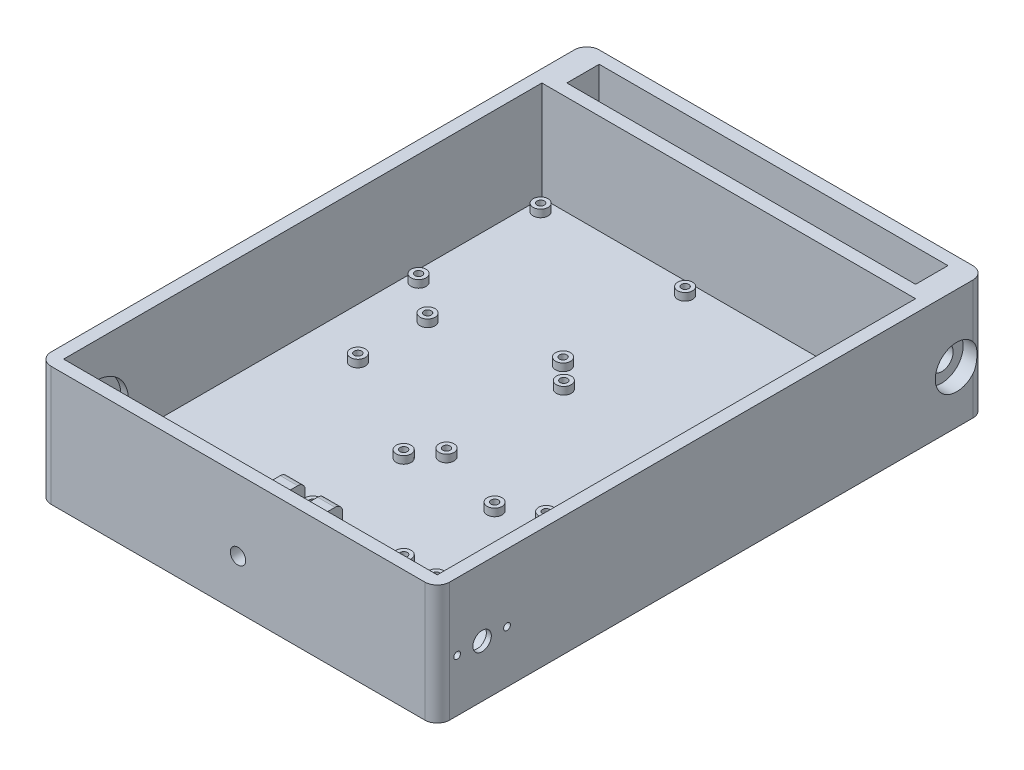
SolidWorks part; units mm, degrees
ref_plane "Front Plane" through (0, 0, 0) normal (0, 0, 1) x (1, 0, 0)
ref_plane "Top Plane" through (0, 0, 0) normal (0, 1, 0) x (1, 0, 0)
ref_plane "Right Plane" through (0, 0, 0) normal (1, 0, 0) x (0, 0, -1)
sketch "Main Body" plane through (0, 0, 0) normal (0, 1, 0) x (1, 0, 0)
  line L0 (-75, 110) -> (75, 110)
  line L1 (-75, -105) -> (75, -105)
  line L2 (-75, -105) -> (-75, 105)
  line L3 (-75, 105) -> (75, 105)
  line L4 (75, -105) -> (75, 105)
  line L5 (-75, -105) -> (75, 105) construction
  line L6 (-75, 105) -> (75, -105) construction
  line L7 (80, -105) -> (80, 105)
  line L8 (-75, -110) -> (75, -110)
  line L9 (-80, -105) -> (-80, 105)
  line L10 (-80, -110) -> (80, -110) construction
  line L11 (-80, -110) -> (-80, 110) construction
  line L12 (80, -110) -> (80, 110) construction
  line L13 (-80, 110) -> (80, 110) construction
  arc A0 (-75, -110) -> (-80, -105) centre (-75, -105) cw
  arc A1 (80, -105) -> (75, -110) centre (75, -105) cw
  arc A2 (75, 110) -> (80, 105) centre (75, 105) cw
  arc A3 (-75, 110) -> (-80, 105) centre (-75, 105) ccw
  point P0 (0, 0)
  dimension "D4" = 5
  dimension "D1" = 75
  dimension "D2" = 210
  dimension "D3" = 5
extrude "Boss-Extrude1" add sketch "Main Body" along normal blind 8 contours L1 L4 L3 L2 | L9 L8 L7 L0 L4 L1 L2 L3 region at (0, 0, -107.2797) region at (0, 0, 0)
extrude "Boss-Extrude3" add sketch "Main Body<4>" along normal blind 40 from surface starting at face at (0, 8, 0)
sketch "Main Body<4>" plane through (0, 0, 0) normal (0, 1, 0) x (1, 0, 0) same geometry as "Main Body"
sketch "Sketch1" plane through (75, 0, 0) normal (-1, 0, 0) x (0, 0, 1)
  line L0 (105, 48) -> (105, 8) construction
  line L1 (-105, 8) -> (105, 8) construction
  line L2 (79, 15.5) -> (105, 15.5)
  line L3 (79, 8) -> (105, 8)
  line L4 (79, 8) -> (79, 34)
  line L5 (79, 34) -> (105, 34)
  line L6 (105, 8) -> (105, 34)
  line L7 (79, 8) -> (105, 34) construction
  line L8 (79, 34) -> (105, 8) construction
  circle A0 centre (92, 21) radius 13
  line M2 (-105, 8) -> (105, 8)
  line M3 (105, 8) -> (105, 48)
  dimension "D1" = 26
  dimension "D2" = 7.5
extrude "Boss-Extrude4" add sketch "Sketch1" along normal up to surface (150 mm away) contours A0 L4 M2 | A0 L3 M3 region at (75, 10.5201, 82.0674) region at (75, 10.5201, 101.9326) up to face at (-75, 28, 0)
sketch "Sketch2" plane through (0, 0, 0) normal (1, 0, 0) x (0, 0, -1)
  line L0 (-105, 48) -> (-105, 15.5) construction
  line L1 (-105, 8) -> (-79, 8)
  line L2 (-105, 8) -> (-105, 15.5)
  line L3 (-105, 15.5) -> (-79, 15.5)
  line L4 (-79, 8) -> (-79, 15.5)
  line L5 (105, 8) -> (-79, 8) construction
  line L6 (-79, 8) -> (-79, 15.5) construction
  line L7 (-79, 15.5) -> (-80.2208, 15.5) construction
extrude "Cut-Extrude1" cut sketch "Sketch2" against normal mid plane 12
sketch "Sketch3" plane through (0, 8, 0) normal (0, 1, 0) x (1, 0, 0)
  line L0 (75, -105) -> (-75, -105) construction
  line L1 (-4, -79) -> (-11, -79)
  line L2 (-4, -79) -> (-4, -105)
  line L3 (-4, -105) -> (-11, -105)
  line L4 (-11, -79) -> (-11, -105)
  line L5 (0, 0) -> (0, -105) construction
  line L6 (-75, -79) -> (-6, -79) construction
  line L7 (11, -79) -> (11, -105)
  line L8 (4, -105) -> (11, -105)
  line L9 (4, -79) -> (4, -105)
  line L10 (4, -79) -> (11, -79)
  line L11 (-6, -103.7792) -> (-6, -92) construction
  dimension "D1" = 5
  dimension "D2" = 4
extrude "Boss-Extrude5" add sketch "Sketch3" along normal blind 20
sketch "Sketch4" plane through (0, 8, 0) normal (0, 1, 0) x (1, 0, 0)
  line L0 (-75, -105) -> (-75, 105) construction
  line L1 (-75, 92) -> (75, 92)
  line L2 (-75, 92) -> (-75, 87)
  line L3 (-75, 87) -> (75, 87)
  line L4 (75, 92) -> (75, 87)
  line L5 (75, 105) -> (75, -105) construction
  line L6 (-75, 105) -> (75, 105) construction
  dimension "D1" = 18
  dimension "D2" = 5
extrude "Boss-Extrude6" add sketch "Sketch4" along normal up to surface (40 mm away) up to face at (0, 48, 0)
sketch "Sketch5" plane through (80, 0, 0) normal (1, 0, 0) x (0, 0, -1)
  circle A0 centre (-92, 21) radius 3.5 construction
  circle A1 centre (-92, 21) radius 3.5
  circle A2 centre (-92, 21) radius 3.7
  dimension "D1" = 0.2
extrude "Cut-Extrude4" cut sketch "Sketch5" against normal up to next contours A1 | A2 A1 region at (80, 21, 92) region at (80, 21, 95.5953)
sketch "Sketch6" plane through (-75, 0, 0) normal (1, 0, 0) x (0, 0, -1)
  circle A0 centre (-92, 21) radius 13
  dimension "D1" = 26
extrude "Cut-Extrude5" cut sketch "Sketch6" against normal offset from surface (3 mm away) 2 up to face at (-80, 24, 0)
mirror "Mirror1" about plane through (0, 0, 0) normal (1, 0, 0) of "Cut-Extrude4"
sketch "Sketch8" plane through (75, 0, 0) normal (-1, 0, 0) x (0, 0, 1)
  circle A0 centre (92, 21) radius 13
  dimension "D1" = 26
extrude "Cut-Extrude6" cut sketch "Sketch8" against normal offset from surface (3 mm away) 2 up to face at (80, 21, 88.3)
sketch "Sketch10" plane through (80, 0, 0) normal (1, 0, 0) x (0, 0, -1)
  circle A1 centre (-82, 21) radius 1.25
  circle A2 centre (-82, 21) radius 1.25
  circle A3 centre (-102, 21) radius 1.25
  circle A4 centre (-102, 21) radius 1.25
  circle A5 centre (-92, 21) radius 12.5
  circle A6 centre (-92, 21) radius 12.5
  circle A63 centre (-102, 21) radius 1.35
  circle A64 centre (-82, 21) radius 1.35
  dimension "D1" = 0
  dimension "D2" = 0
  dimension "D3" = 0
  dimension "D4" = 0.1
  dimension "D5" = 0.1
extrude "Cut-Extrude7" cut sketch "Sketch10" against normal up to next contours A2 | A64 A2 | A4 | A63 A4 region at (80, 21, 82) region at (80, 21, 102) region at (80, 21, 103.3118) region at (80, 21, 83.3118)
mirror "Mirror3" about plane through (0, 0, 0) normal (1, 0, 0) of "Cut-Extrude7"
sketch "Sketch11" plane through (80, 0, 0) normal (1, 0, 0) x (0, 0, -1)
  circle A0 centre (98.5, 21) radius 4.5 construction
  circle A1 centre (98.5, 21) radius 4.5
  circle A3 centre (98.5, 21) radius 4.6
  dimension "D1" = 0.1
extrude "Cut-Extrude10" cut sketch "Sketch11" against normal through all contours A1 | A3 A1 region at (80, 21, -98.5) region at (80, 21, -93.913)
sketch "Sketch12" plane through (-75, 0, 0) normal (1, 0, 0) x (0, 0, -1)
  line L0 (92, 8) -> (105, 8) construction
  line L1 (92, 48) -> (105, 48)
  line L2 (92, 48) -> (92, 8)
  line L3 (92, 8) -> (105, 8)
  line L4 (105, 48) -> (105, 8)
  line L6 (92, 48) -> (92, 8) construction
  line L7 (92, 48) -> (105, 48) construction
  circle A2 centre (98.5, 21) radius 4.6 construction
  circle A3 centre (98.5, 21) radius 4.6
extrude "Boss-Extrude7" add sketch "Sketch12" along normal blind 5
sketch "Sketch13" plane through (-80, 0, 0) normal (-1, 0, 0) x (0, 0, 1)
  circle A0 centre (-98.5, 21) radius 8.6
  circle A2 centre (-98.5, 21) radius 4.6 construction
  dimension "D1" = 17.2
extrude "Cut-Extrude11" cut sketch "Sketch13" against normal blind 6
mirror "Mirror4" about plane through (0, 0, 0) normal (1, 0, 0) of "Boss-Extrude7", "Cut-Extrude11"
sketch "Sketch14" plane through (0, 8, 0) normal (0, 1, 0) x (1, 0, 0)
  line L0 (-4, -105) -> (-4, -79) construction
  line L1 (-4, -95) -> (4, -95)
  line L2 (-4, -95) -> (-4, -105)
  line L3 (-4, -105) -> (4, -105)
  line L4 (4, -95) -> (4, -105)
  dimension "D1" = 10
extrude "Boss-Extrude9" add sketch "Sketch14" along normal blind 5
sketch "Sketch15" plane through (0, 0, 110) normal (0, 0, 1) x (1, 0, 0)
  arc A0 (-3, 19.5) -> (3, 19.5) centre (0, 19.5) ccw construction
  arc A1 (-3, 19.5) -> (3, 19.5) centre (0, 19.5) ccw
  arc A2 (3, 19.5) -> (-3, 19.5) centre (0, 19.5) ccw construction
  arc A3 (3, 19.5) -> (-3, 19.5) centre (0, 19.5) ccw
  arc A4 (3.1, 19.5) -> (-3.1, 19.5) centre (0, 19.5) ccw
  arc A5 (-3.1, 19.5) -> (3.1, 19.5) centre (0, 19.5) ccw
  dimension "D1" = 0.1
extrude "Cut-Extrude12" cut sketch "Sketch15" against normal up to next contours A1 A3 | A4 A5 A3 A1 region at (0, 19.5, 110) region at (0, 16.4877, 110)
fillet "Fillet1" radius 3 7 edges at (-4, 8, 87) (4, 8, 87) (0, 8, 95) (7.5, 28, 105) (-7.5, 28, 105) (-7.5, 28, 79) (7.5, 28, 79)
sketch "Sketch16" plane through (0, 0, 0) normal (0, -1, 0) x (1, 0, 0)
  circle A0 centre (-12.5, -82) radius 1.475 construction
  circle A1 centre (-70.5, -82) radius 1.475 construction
  circle A2 centre (-70.5, -33) radius 1.475 construction
  circle A3 centre (-12.5, -33) radius 1.475 construction
  circle A4 centre (-4.2, -25) radius 1.475 construction
  circle A5 centre (-55, -21.12) radius 1.475 construction
  circle A6 centre (-55, 6.88) radius 1.475 construction
  circle A7 centre (-4.2, 22.08) radius 1.475 construction
  circle A8 centre (-12.3, 31.18) radius 1.475 construction
  circle A9 centre (24.2, 31.18) radius 1.475 construction
  circle A10 centre (37.8459, 24.117) radius 1.475 construction
  circle A11 centre (59.5541, 24.117) radius 1.475 construction
  circle A12 centre (59.5541, 68.243) radius 1.475 construction
  circle A13 centre (37.8459, 68.243) radius 1.475 construction
  circle A14 centre (24.2, 67.68) radius 1.475 construction
  circle A15 centre (-12.3, 67.68) radius 1.475 construction
  circle A16 centre (-12.5, -82) radius 1.475
  circle A17 centre (-70.5, -82) radius 1.475
  circle A18 centre (-70.5, -33) radius 1.475
  circle A19 centre (-12.5, -33) radius 1.475
  circle A20 centre (-4.2, -25) radius 1.475
  circle A21 centre (-55, -21.12) radius 1.475
  circle A22 centre (-55, 6.88) radius 1.475
  circle A23 centre (-4.2, 22.08) radius 1.475
  circle A24 centre (-12.3, 31.18) radius 1.475
  circle A25 centre (24.2, 31.18) radius 1.475
  circle A26 centre (37.8459, 24.117) radius 1.475
  circle A27 centre (59.5541, 24.117) radius 1.475
  circle A28 centre (59.5541, 68.243) radius 1.475
  circle A29 centre (37.8459, 68.243) radius 1.475
  circle A30 centre (24.2, 67.68) radius 1.475
  circle A31 centre (-12.3, 67.68) radius 1.475
extrude "Cut-Extrude13" cut sketch "Sketch16" against normal up to next
sketch "Sketch17" plane through (0, 8, 0) normal (0, 1, 0) x (1, 0, 0)
  line L0 (0, 87) -> (0, -110) construction
  line L1 (-75, 87) -> (75, 87) construction
  line L2 (75, -110) -> (-75, -110) construction
  line L3 (-75, 4) -> (75, 4) construction
  line L7 (-75, -79) -> (-75, 87) construction
  line L8 (75, 87) -> (75, -79) construction
  circle A0 centre (-70.5, 82) radius 3
  circle A1 centre (-12.5, 82) radius 3
  circle A2 centre (-12.3, -67.68) radius 1.475
  circle A3 centre (-12.3, -67.68) radius 1.475
  circle A4 centre (24.2, -67.68) radius 1.475
  circle A5 centre (24.2, -67.68) radius 1.475
  circle A6 centre (37.8459, -68.243) radius 1.475
  circle A7 centre (37.8459, -68.243) radius 1.475
  circle A8 centre (59.5541, -68.243) radius 1.475
  circle A9 centre (59.5541, -68.243) radius 1.475
  circle A10 centre (59.5541, -24.117) radius 1.475
  circle A11 centre (59.5541, -24.117) radius 1.475
  circle A12 centre (37.8459, -24.117) radius 1.475
  circle A13 centre (37.8459, -24.117) radius 1.475
  circle A14 centre (24.2, -31.18) radius 1.475
  circle A15 centre (24.2, -31.18) radius 1.475
  circle A16 centre (-12.3, -31.18) radius 1.475
  circle A17 centre (-12.3, -31.18) radius 1.475
  circle A18 centre (-4.2, -22.08) radius 1.475
  circle A19 centre (-4.2, -22.08) radius 1.475
  circle A20 centre (-55, -6.88) radius 1.475
  circle A21 centre (-55, -6.88) radius 1.475
  circle A22 centre (-55, 21.12) radius 1.475
  circle A23 centre (-55, 21.12) radius 1.475
  circle A24 centre (-4.2, 25) radius 1.475
  circle A25 centre (-4.2, 25) radius 1.475
  circle A26 centre (-12.5, 33) radius 1.475
  circle A27 centre (-12.5, 33) radius 1.475
  circle A28 centre (-70.5, 33) radius 1.475
  circle A29 centre (-70.5, 33) radius 1.475
  circle A30 centre (-70.5, 82) radius 1.475
  circle A31 centre (-70.5, 82) radius 1.475
  circle A32 centre (-12.5, 82) radius 1.475
  circle A33 centre (-12.5, 82) radius 1.475
  circle A34 centre (-70.5, 33) radius 3
  circle A35 centre (-55, 21.12) radius 3
  circle A36 centre (-12.5, 33) radius 3
  circle A37 centre (-4.2, 25) radius 3
  circle A38 centre (-55, -6.88) radius 3
  circle A39 centre (-4.2, -22.08) radius 3
  circle A40 centre (-12.3, -31.18) radius 3
  circle A41 centre (24.2, -31.18) radius 3
  circle A42 centre (37.8459, -24.117) radius 3
  circle A43 centre (59.5541, -24.117) radius 3
  circle A44 centre (-12.3, -67.68) radius 3
  circle A45 centre (24.2, -67.68) radius 3
  circle A46 centre (37.8459, -68.243) radius 3
  circle A47 centre (59.5541, -68.243) radius 3
  point P78 (0, 0)
  dimension "D1" = 6
  dimension "D2" = 0
  dimension "D3" = 0
  dimension "D4" = 0
  dimension "D5" = 0
  dimension "D6" = 0
  dimension "D7" = 0
  dimension "D8" = 0
  dimension "D9" = 0
  dimension "D10" = 0
  dimension "D11" = 0
  dimension "D12" = 0
  dimension "D13" = 0
  dimension "D14" = 0
  dimension "D15" = 0
  dimension "D16" = 0
  dimension "D17" = 0
extrude "Boss-Extrude10" add sketch "Sketch17" along normal blind 3
